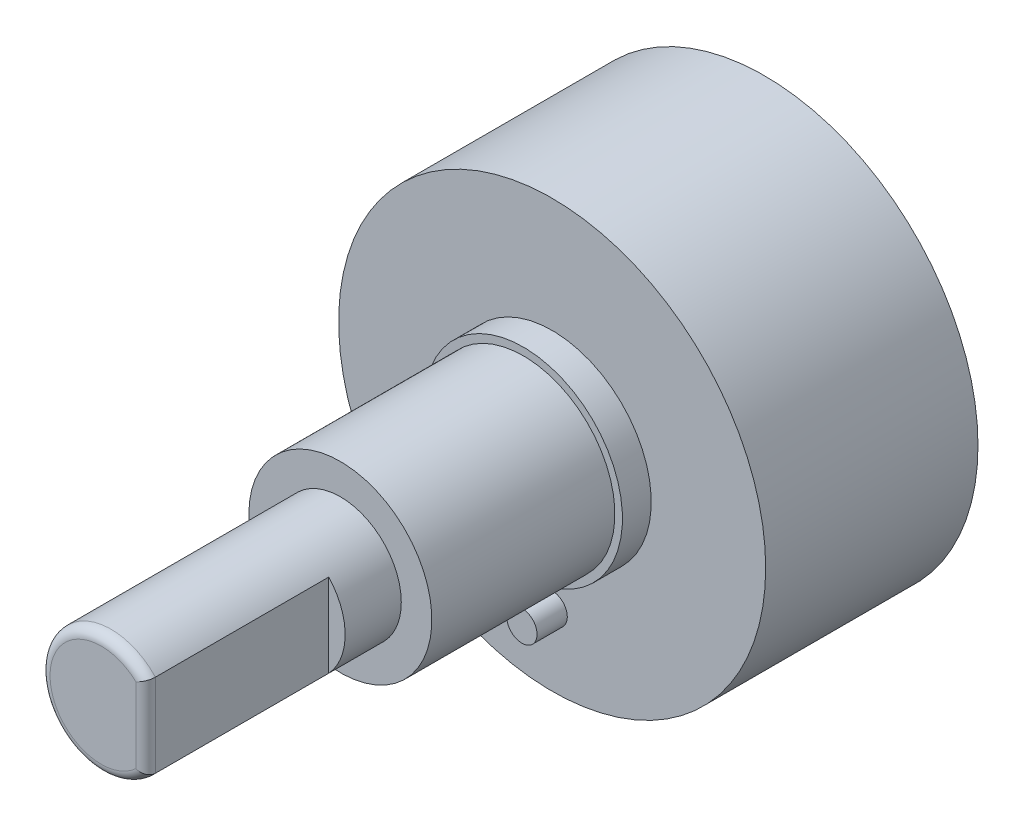
SolidWorks part; units mm, degrees
ref_plane "Front Plane" through (0, 0, 0) normal (0, 0, 1) x (1, 0, 0)
ref_plane "Top Plane" through (0, 0, 0) normal (0, 1, 0) x (1, 0, 0)
ref_plane "Right Plane" through (0, 0, 0) normal (1, 0, 0) x (0, 0, -1)
sketch "Sketch1" plane through (0, 0, 0) normal (0, 0, 1) x (1, 0, 0)
  circle A0 centre (0, 0) radius 11.1125
  dimension "D1" = 22.225
extrude "Boss-Extrude1" add sketch "Sketch1" against normal blind 11.049
sketch "Sketch2" plane through (0, 0, 0) normal (0, 0, 1) x (1, 0, 0)
  circle A0 centre (0, 0) radius 5.1562
  dimension "D1" = 10.3124
extrude "Boss-Extrude2" add sketch "Sketch2" along normal blind 1.4986
sketch "Sketch3" plane through (0, 0, 1.4986) normal (0, 0, 1) x (1, 0, 0)
  circle A0 centre (0, 0) radius 4.7625
  dimension "D1" = 9.525
extrude "Boss-Extrude3" add sketch "Sketch3" along normal blind 9.525
cosmetic thread "Cosmetic Thread1" parameters "D2"=8.2652
sketch "Sketch4" plane through (0, 0, 11.0236) normal (0, 0, 1) x (1, 0, 0)
  circle A0 centre (0, 0) radius 3.1712
  dimension "D1" = 6.3424
extrude "Boss-Extrude5" add sketch "Sketch4" along normal blind 12.446
sketch "Sketch5" plane through (0, 0, 23.4696) normal (0, 0, 1) x (1, 0, 0)
  line L0 (2.3152, -2.1671) -> (2.3152, 2.1671)
  circle A0 centre (0, 0) radius 3.1712 construction
  circle A1 centre (0, 0) radius 3.1712 construction
  arc A2 (2.3152, -2.1671) -> (2.3152, 2.1671) centre (0, 0) ccw
  point P4 (-3.1712, 0)
  dimension "D1" = 5.4864
extrude "Cut-Extrude1" cut sketch "Sketch5" against normal blind 9.525
sketch "Sketch6" plane through (0, 0, 0) normal (0, 0, 1) x (1, 0, 0)
  circle A0 centre (0, -7.366) radius 0.7874
  dimension "D1" = 1.5748
  dimension "D2" = 7.366
extrude "Boss-Extrude6" add sketch "Sketch6" along normal blind 1.5748
sketch "Sketch7" plane through (0, 0, -11.049) normal (0, 0, -1) x (-1, 0, 0)
  circle A0 centre (0, 0) radius 5.5245 construction
  circle A1 centre (0, -5.5245) radius 0.7874
  circle A2 centre (-3.9116, 3.9012) radius 0.7874
  circle A3 centre (3.9116, 3.9012) radius 0.7874
  dimension "D1" = 11.049
  dimension "D2" = 1.5748
  dimension "D3" = 7.8232
extrude "Boss-Extrude7" add sketch "Sketch7" along normal blind 3.175
sketch "Sketch8" plane through (0, 0, -11.049) normal (0, 0, -1) x (-1, 0, 0)
  line L0 (-3.9116, 3.9012) -> (-3.9116, 1.3612) construction
  line L1 (-6.9303, 1.3612) -> (-0.8929, 1.3612) construction
  line L2 (3.9116, 3.9012) -> (3.9116, 1.3612) construction
  line L3 (0.7377, 1.3612) -> (7.0855, 1.3612) construction
  line L4 (0, -5.5245) -> (0, -8.0645) construction
  line L5 (-2.9091, -8.0645) -> (2.9091, -8.0645) construction
  text T0 "<b>GND</b>" font "Century Gothic" height 1.27
  text T1 "<b>+5V</b>" font "Century Gothic" height 1.27
  text T2 "<b>Vout</b>" font "Century Gothic" height 1.27
  point P13 (-3.9116, 1.3612)
  point P16 (3.9116, 1.3612)
  point P19 (0, -8.0645)
wrap "Wrap1" sketch "Sketch8" wrap type scribe source sketch "Sketch8" face at (-3.1242, 3.9012, -11.049)
fillet "Fillet1" radius 0.508 2 edges at (-3.1712, 0, 23.4696) (2.3152, 0, 23.4696)
